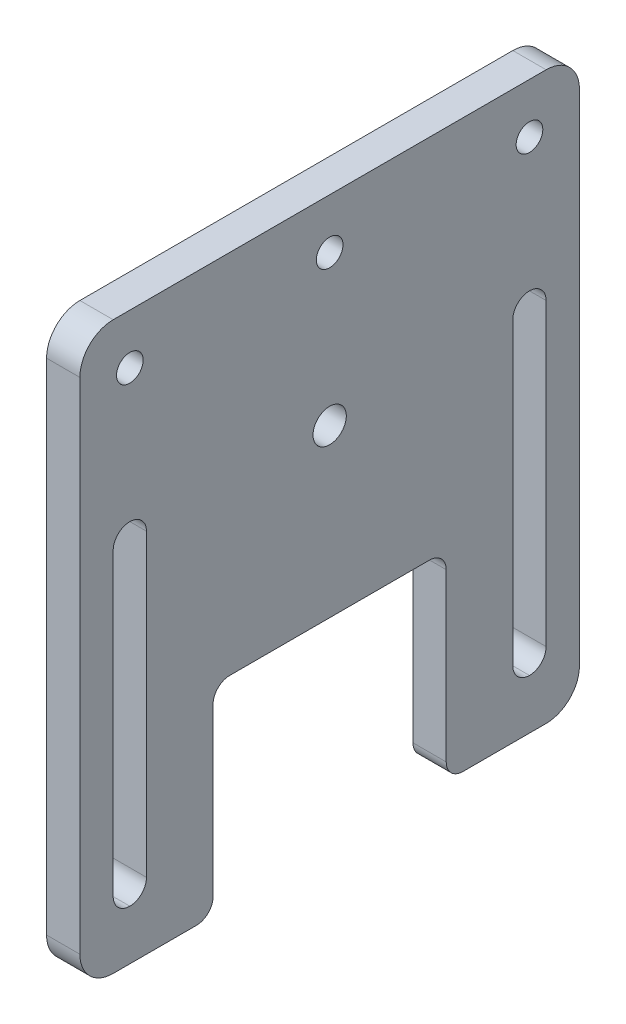
SolidWorks part; units mm, degrees
material "7075-T6 (SN)"
ref_plane "Front Plane" through (0, 0, 0) normal (0, 0, 1) x (1, 0, 0)
ref_plane "Top Plane" through (0, 0, 0) normal (0, 1, 0) x (1, 0, 0)
ref_plane "Right Plane" through (0, 0, 0) normal (1, 0, 0) x (0, 0, -1)
sketch "Sketch1" plane through (0, 0, 0) normal (1, 0, 0) x (0, 0, -1)
  line L1 (-75, -85) -> (75, -85)
  line L2 (-75, -85) -> (-75, 85)
  line L3 (-75, 85) -> (75, 85)
  line L4 (75, -85) -> (75, 85)
  line L5 (-75, -85) -> (75, 85) construction
  line L6 (-75, 85) -> (75, -85) construction
  point P0 (0, 0)
  dimension "D1" = 150
  dimension "D2" = 170
extrude "Boss-Extrude1" add sketch "Sketch1" along normal blind 10
sketch "Sketch4" plane through (0, 0, 0) normal (-1, 0, 0) x (0, 0, 1)
  line L0 (-75, 85) -> (75, 85) construction
  line L1 (-75, -85) -> (-75, 85) construction
  line L2 (75, -85) -> (-75, -85) construction
  line L3 (-55, 30) -> (55, 30) construction
  line L4 (-40, -85) -> (40, -85)
  line L5 (75, 85) -> (75, -85) construction
  line L10 (55, 30) -> (65, 30)
  line L11 (55, 30) -> (55, -70)
  line L12 (55, -70) -> (65, -70)
  line L13 (65, 30) -> (65, -70)
  line L14 (-35, -80) -> (-35, -30)
  line L15 (-30, -25) -> (30, -25)
  line L16 (-55, 30) -> (-65, 30)
  line L17 (-55, 30) -> (-55, -70)
  line L18 (-55, -70) -> (-65, -70)
  line L19 (-65, 30) -> (-65, -70)
  line L20 (35, -80) -> (35, -30)
  circle A0 centre (-60, 70) radius 4
  circle A2 centre (0, 70) radius 4
  circle A5 centre (60, 70) radius 4
  circle A6 centre (0, 25) radius 5
  arc A7 (-40, -85) -> (-35, -80) centre (-40, -80) ccw
  arc A8 (-35, -30) -> (-30, -25) centre (-30, -30) cw
  arc A9 (40, -85) -> (35, -80) centre (40, -80) cw
  arc A10 (35, -30) -> (30, -25) centre (30, -30) ccw
  point P21 (0, -85)
  point P22 (0, -85)
  dimension "D1" = 8
  dimension "D2" = 60
  dimension "D11" = 10
  dimension "D13" = 5
  dimension "D3" = 15
  dimension "D4" = 15
  dimension "D5" = 10
  dimension "D6" = 100
  dimension "D7" = 10
  dimension "D8" = 10
  dimension "D9" = 15
  dimension "D10" = 60
  dimension "D12" = 80
  dimension "D14" = 60
extrude "Cut-Extrude1" cut sketch "Sketch4" against normal through all both and the other way through all
fillet "Fillet1" radius 5 8 edges at (5, 30, 55) (5, 30, 65) (5, -70, 65) (5, -70, 55) (5, 30, -65) (5, 30, -55) (5, -70, -55) (5, -70, -65)
fillet "Fillet2" radius 10 4 edges at (5, -85, 75) (5, -85, -75) (5, 85, -75) (5, 85, 75)
